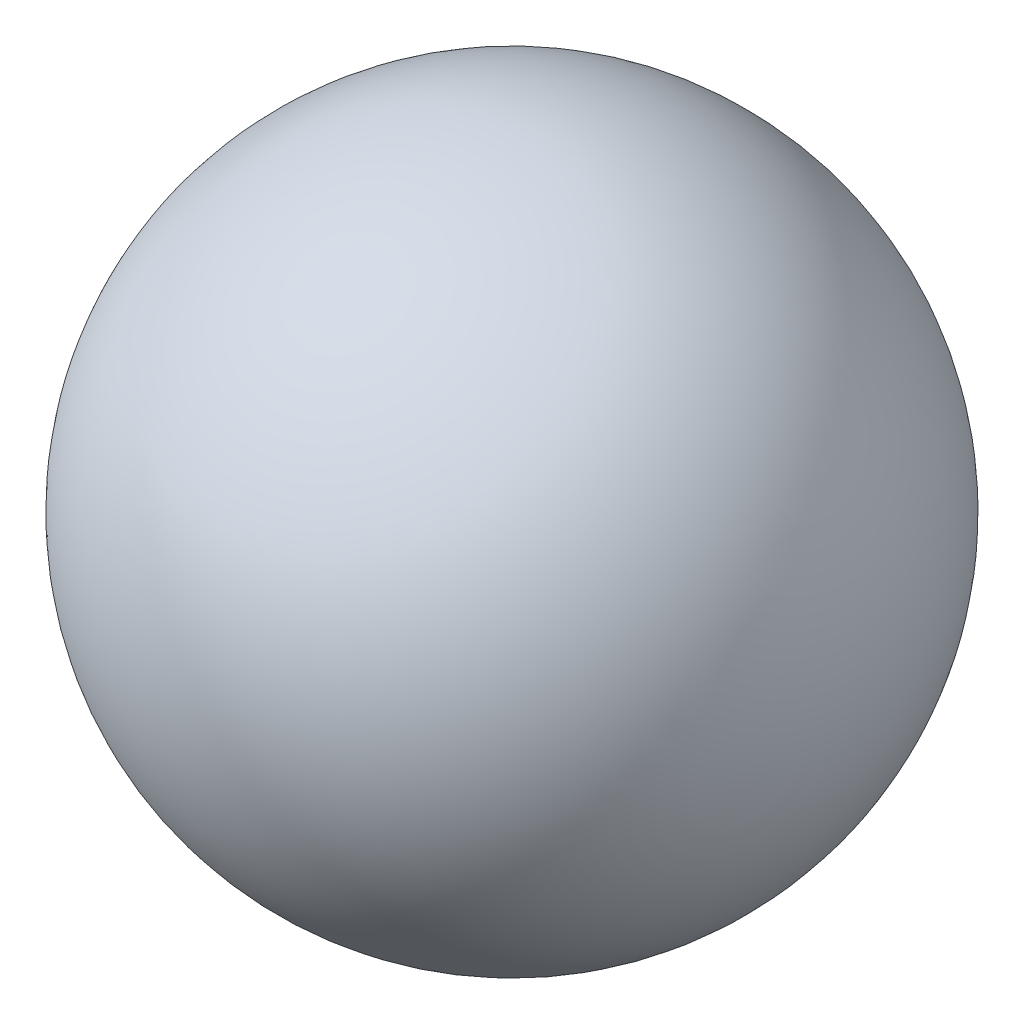
SolidWorks part; units mm, degrees
ref_plane "Front Plane" through (0, 0, 0) normal (0, 0, 1) x (1, 0, 0)
ref_plane "Top Plane" through (0, 0, 0) normal (0, 1, 0) x (1, 0, 0)
ref_plane "Right Plane" through (0, 0, 0) normal (1, 0, 0) x (0, 0, -1)
sketch "Sketch1" plane through (0, 0, 0) normal (0, 0, 1) x (1, 0, 0)
  line L0 (-21, 0) -> (21, 0)
  arc A1 (-21, 0) -> (21, 0) centre (0, 0) ccw
  point P5 (27.9336, 0)
  dimension "D1" = 42
revolve "Revolve1" add sketch "Sketch1" angle 360 about L0 region at (0, -8.9127, 0)
